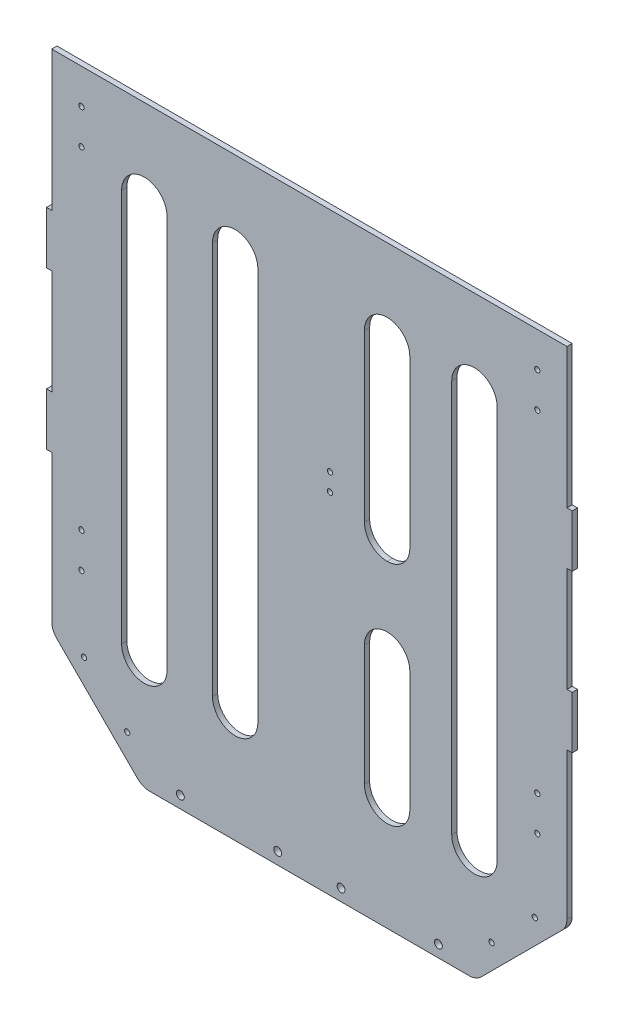
SolidWorks part; units mm, degrees
ref_plane "前视基准面" through (0, 0, 0) normal (0, 0, 1) x (1, 0, 0)
ref_plane "上视基准面" through (0, 0, 0) normal (0, 1, 0) x (1, 0, 0)
ref_plane "右视基准面" through (0, 0, 0) normal (1, 0, 0) x (0, 0, -1)
sketch "草图1" plane through (0, 0, 0) normal (0, 0, 1) x (1, 0, 0)
  line L0 (-147.5, 90) -> (-150.5, 90)
  line L1 (-147.5, 170) -> (147.5, 170)
  line L2 (-147.5, 170) -> (-147.5, 90)
  line L3 (-147.5, -170) -> (147.5, -170)
  line L4 (147.5, 170) -> (147.5, 90)
  line L5 (-147.5, 170) -> (147.5, -170) construction
  line L6 (-147.5, -170) -> (147.5, 170) construction
  line L7 (-150.5, 90) -> (-150.5, 60)
  line L8 (-150.5, 60) -> (-147.5, 60)
  line L9 (-147.5, 60) -> (-147.5, 0)
  line L10 (-147.5, 0) -> (-150.5, 0)
  line L11 (-150.5, 0) -> (-150.5, -30)
  line L12 (-150.5, -30) -> (-147.5, -30)
  line L13 (-147.5, -90) -> (-150.5, -90) construction
  line L14 (-150.5, -90) -> (-150.5, -120) construction
  line L15 (-150.5, -120) -> (-147.5, -120) construction
  line L16 (-147.5, -30) -> (-147.5, -90)
  line L17 (-147.5, -120) -> (-147.5, -170)
  line L18 (0, 0) -> (0, 121.9272) construction
  line L19 (147.5, -90) -> (150.5, -90) construction
  line L20 (150.5, -90) -> (150.5, -120) construction
  line L21 (150.5, -120) -> (147.5, -120) construction
  line L22 (147.5, 0) -> (150.5, 0)
  line L23 (150.5, 0) -> (150.5, -30)
  line L24 (150.5, -30) -> (147.5, -30)
  line L25 (147.5, 90) -> (150.5, 90)
  line L26 (150.5, 90) -> (150.5, 60)
  line L27 (150.5, 60) -> (147.5, 60)
  line L28 (147.5, -120) -> (147.5, -170)
  line L29 (147.5, -30) -> (147.5, -90)
  line L30 (147.5, 60) -> (147.5, 0)
  line L31 (-147.5, -90) -> (-147.5, -120)
  line L32 (147.5, -90) -> (147.5, -120)
  point P0 (0, 0)
  dimension "D1" = 295
  dimension "D2" = 340
  dimension "D3" = 30
  dimension "D4" = 3
  dimension "D5" = 80
  dimension "D6" = 3
  dimension "D7" = 30
  dimension "D8" = 30
  dimension "D9" = 3
  dimension "D10" = 50
  dimension "D11" = 60
extrude "凸台-拉伸1" add sketch "草图1" along normal blind 3
sketch "草图3" plane through (0, 0, 3) normal (0, 0, 1) x (1, 0, 0)
  line L0 (-147.5, -118) -> (-95.5, -170)
  line L1 (-147.5, -30) -> (-147.5, -170) construction
  line L2 (-147.5, -170) -> (147.5, -170) construction
  line L3 (-95.5, -170) -> (-147.5, -170)
  line L4 (-147.5, -170) -> (-147.5, -118)
  line L5 (147.5, -170) -> (147.5, -118)
  line L6 (147.5, -170) -> (147.5, -30) construction
  line L7 (147.5, -118) -> (95.5, -170)
  line L8 (95.5, -170) -> (147.5, -170)
  dimension "D1" = 52
  dimension "D2" = 52
  dimension "D3" = 52
  dimension "D4" = 52
extrude "切除-拉伸2" cut sketch "草图3" against normal through all
fillet "圆角1" [suppressed] radius 5
sketch "草图2" plane through (0, 0, 3) normal (0, 0, 1) x (1, 0, 0)
  line L0 (-95.5, -170) -> (95.5, -170) construction
  line L1 (0, -170) -> (0, -88.9982) construction
  circle A2 centre (73.85, -163.15) radius 2.25 construction
  circle A3 centre (18.15, -163.15) radius 2.25 construction
  circle A4 centre (-73.85, -163.15) radius 2.25 construction
  circle A5 centre (-18.15, -163.15) radius 2.25 construction
  circle A6 centre (11.8005, 40) radius 1.5
  circle A7 centre (11.8005, 30) radius 1.5
  circle A8 centre (73.85, -163.15) radius 2.25 construction
  circle A9 centre (18.15, -163.15) radius 2.25 construction
  circle A10 centre (-73.85, -163.15) radius 2.25 construction
  circle A11 centre (-18.15, -163.15) radius 2.25 construction
  circle A12 centre (-73.85, -163.15) radius 2.25
  circle A13 centre (-18.15, -163.15) radius 2.25
  circle A14 centre (18.15, -163.15) radius 2.25
  circle A15 centre (73.85, -163.15) radius 2.25
  dimension "D1" = 4.5
  dimension "D2" = 4.5
  dimension "D5" = 3
  dimension "D6" = 3
  dimension "D3" = 55.7
  dimension "D4" = 18.15
extrude "切除-拉伸1" cut sketch "草图2" against normal blind 10
sketch "草图4" plane through (0, 0, 3) normal (0, 0, 1) x (1, 0, 0)
  line L0 (147.5, 170) -> (-147.5, 170) construction
  line L1 (147.5, 90) -> (147.5, 170) construction
  line L2 (147.5, -118) -> (147.5, -30) construction
  line L3 (0, 170) -> (0, 113.7599) construction
  circle A0 centre (130.5, 150) radius 1.5
  circle A1 centre (130.5, 130) radius 1.5
  circle A2 centre (130.5, -60) radius 1.5
  circle A3 centre (130.5, -80) radius 1.5
  circle A4 centre (-130.5, -80) radius 1.5
  circle A5 centre (-130.5, -60) radius 1.5
  circle A6 centre (-130.5, 130) radius 1.5
  circle A7 centre (-130.5, 150) radius 1.5
  dimension "D1" = 20
  dimension "D2" = 20
  dimension "D3" = 190
  dimension "D4" = 20
  dimension "D5" = 17
  dimension "D6" = 17
  dimension "D7" = 17
  dimension "D8" = 17
  dimension "D9" = 3
  dimension "D10" = 3
  dimension "D11" = 3
  dimension "D12" = 3
extrude "切除-拉伸3" cut sketch "草图4" against normal through all
sketch "草图5" plane through (0, 0, 3) normal (0, 0, 1) x (1, 0, 0)
  line L0 (-94.5, 120) -> (-94.5, -105) construction
  line L1 (-81.5, 120) -> (-81.5, -105)
  line L2 (-107.5, 120) -> (-107.5, -105)
  line L3 (147.5, 170) -> (-147.5, 170) construction
  line L4 (-147.5, 60) -> (-147.5, 0) construction
  line L5 (-42.5, 120) -> (-42.5, -105) construction
  line L6 (-29.5, 120) -> (-29.5, -105)
  line L7 (-55.5, 120) -> (-55.5, -105)
  line L8 (44.5, 120) -> (44.5, -105) construction
  line L9 (57.5, 120) -> (57.5, -105)
  line L10 (31.5, 120) -> (31.5, -105)
  line L11 (94.5, 120) -> (94.5, -105) construction
  line L12 (107.5, 120) -> (107.5, -105)
  line L13 (81.5, 120) -> (81.5, -105)
  arc A0 (-81.5, 120) -> (-107.5, 120) centre (-94.5, 120) ccw
  arc A1 (-107.5, -105) -> (-81.5, -105) centre (-94.5, -105) ccw
  arc A2 (-29.5, 120) -> (-55.5, 120) centre (-42.5, 120) ccw
  arc A3 (-55.5, -105) -> (-29.5, -105) centre (-42.5, -105) ccw
  arc A4 (57.5, 120) -> (31.5, 120) centre (44.5, 120) ccw
  arc A5 (31.5, -105) -> (57.5, -105) centre (44.5, -105) ccw
  arc A6 (107.5, 120) -> (81.5, 120) centre (94.5, 120) ccw
  arc A7 (81.5, -105) -> (107.5, -105) centre (94.5, -105) ccw
  point P2 (-94.5, 7.5)
  point P14 (-42.5, 7.5)
  point P22 (44.5, 7.5)
  point P29 (94.5, 7.5)
  dimension "D1" = 13
  dimension "D2" = 225
  dimension "D3" = 50
  dimension "D4" = 53
  dimension "D8" = 52
  dimension "D9" = 87
  dimension "D5" = 2
  dimension "D6" = 2
  dimension "D7" = 2
extrude "切除-拉伸4" cut sketch "草图5" against normal through all
sketch "草图6" plane through (0, 0, 3) normal (0, 0, 1) x (1, 0, 0)
  line L0 (31.5, 120) -> (31.5, -105) construction
  line L1 (31.5, 12) -> (57.5, 12)
  line L2 (31.5, 12) -> (31.5, -23)
  line L3 (31.5, -23) -> (57.5, -23)
  line L4 (57.5, 12) -> (57.5, -23)
  line L5 (57.5, -105) -> (57.5, 120) construction
  arc A0 (57.5, 120) -> (31.5, 120) centre (44.5, 120) ccw construction
  dimension "D1" = 35
  dimension "D2" = 108
extrude "凸台-拉伸2" add sketch "草图6" against normal up to surface (3 mm away) up to face at (-42.5, 7.5, 0)
fillet "圆角2" radius 13 4 edges at (57.5, -23, 1.5) (31.5, -23, 1.5) (57.5, 12, 1.5) (31.5, 12, 1.5)
sketch "草图7" plane through (0, 0, 3) normal (0, 0, 1) x (1, 0, 0)
  line L0 (0.5, 120) -> (0.5, 35) construction
  line L1 (10.5, 120) -> (10.5, 35)
  line L2 (-9.5, 120) -> (-9.5, 35)
  line L3 (31.5, 120) -> (31.5, 25) construction
  arc A0 (10.5, 120) -> (-9.5, 120) centre (0.5, 120) ccw
  arc A1 (-9.5, 35) -> (10.5, 35) centre (0.5, 35) ccw
  point P2 (0.5, 77.5)
  dimension "D1" = 10
  dimension "D2" = 21
  dimension "D3" = 85
fillet "圆角3" radius 10 4 edges at (147.5, -118, 1.5) (95.5, -170, 1.5) (-95.5, -170, 1.5) (-147.5, -118, 1.5)
sketch "草图8" plane through (0, 0, 3) normal (0, 0, 1) x (1, 0, 0)
  line L0 (-129.0441, -122.3138) -> (-104.2954, -147.0625) construction
  line L1 (-98.4289, -167.0711) -> (-144.5711, -120.9289) construction
  line L2 (-147.5, -99.7493) -> (147.5, -99.7493) construction
  line L3 (-147.5, -30) -> (-147.5, -113.8579) construction
  line L4 (147.5, -113.8579) -> (147.5, -30) construction
  line L5 (0, -99.7493) -> (0, -54.3911) construction
  line L6 (129.0441, -122.3138) -> (104.2954, -147.0625) construction
  circle A0 centre (-129.0441, -122.3138) radius 1.5
  circle A1 centre (-104.2954, -147.0625) radius 1.5
  circle A2 centre (104.2954, -147.0625) radius 1.5
  circle A3 centre (129.0441, -122.3138) radius 1.5
  dimension "D1" = 3
  dimension "D2" = 3
  dimension "D3" = 10
  dimension "D4" = 35
extrude "切除-拉伸5" cut sketch "草图8" against normal through all
